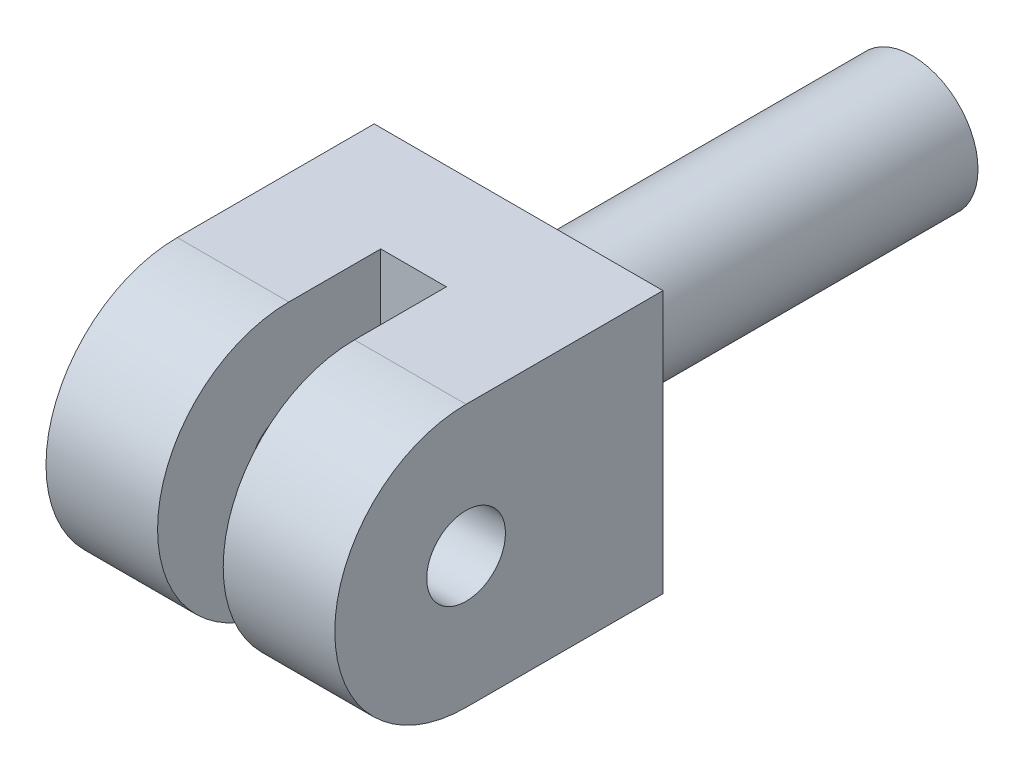
SolidWorks part; units mm, degrees
ref_plane "Ön Düzlem" through (0, 0, 0) normal (0, 0, 1) x (1, 0, 0)
ref_plane "Üst Düzlem" through (0, 0, 0) normal (0, 1, 0) x (1, 0, 0)
ref_plane "Sağ Düzlem" through (0, 0, 0) normal (1, 0, 0) x (0, 0, -1)
sketch "Sketch1" plane through (0, 0, 0) normal (1, 0, 0) x (0, 0, -1)
  line L1 (0, 0) -> (25, 0)
  line L2 (0, 0) -> (0, 20)
  line L3 (0, 20) -> (25, 20)
  line L4 (25, 0) -> (25, 20)
  dimension "D1" = 20
  dimension "D2" = 25
extrude "Boss-Extrude1" add sketch "Sketch1" along normal blind 22
fillet "Fillet1" 2 edges at (11, 20, 0) (11, 0, 0) type full round first side face at (11, 20, -12.5) second side face at (11, 0, -12.5) middle face at (11, 10, 0)
sketch "Sketch2" plane through (0, 0, -25) normal (0, 0, -1) x (-1, 0, 0)
  line L1 (-22, 0) -> (0, 0) construction
  line L2 (0, 0) -> (0, 20) construction
  circle A0 centre (-11, 10) radius 5
  dimension "D1" = 10
  dimension "D2" = 11
extrude "Boss-Extrude2" add sketch "Sketch2" along normal blind 30
sketch "Sketch3" plane through (22, 0, 0) normal (1, 0, 0) x (0, 0, -1)
  circle A0 centre (10, 10) radius 3
extrude "Cut-Extrude1" cut sketch "Sketch3" against normal blind 30
sketch "Sketch4" plane through (0, 20, 0) normal (0, 1, 0) x (1, 0, 0)
  line L0 (0, 0) -> (22, 0) construction
  line L1 (8.5, -17) -> (13.5, -17)
  line L2 (8.5, -17) -> (8.5, 17)
  line L3 (8.5, 17) -> (13.5, 17)
  line L4 (13.5, -17) -> (13.5, 17)
  line L5 (8.5, -17) -> (13.5, 17) construction
  line L6 (8.5, 17) -> (13.5, -17) construction
  line L7 (22, 25) -> (0, 25) construction
  point P0 (11, 0)
  dimension "D1" = 5
  dimension "D2" = 8
extrude "Cut-Extrude2" cut sketch "Sketch4" against normal blind 31
